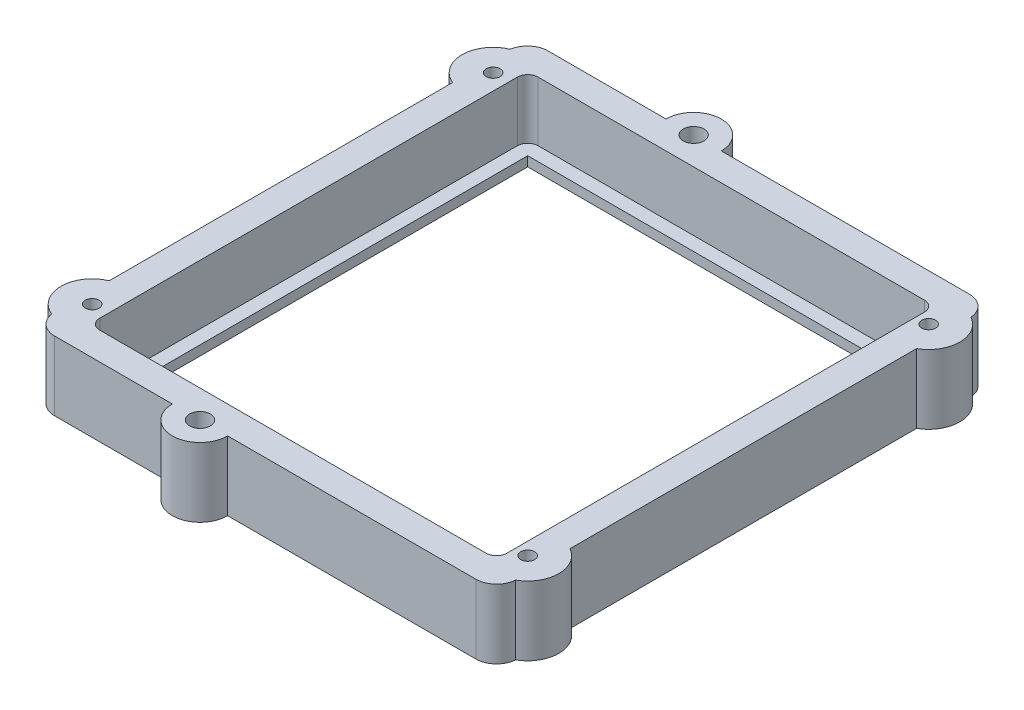
SolidWorks part; units mm, degrees
ref_plane "Спереди" through (0, 0, 0) normal (0, 0, 1) x (1, 0, 0)
ref_plane "Сверху" through (0, 0, 0) normal (0, 1, 0) x (1, 0, 0)
ref_plane "Справа" through (0, 0, 0) normal (1, 0, 0) x (0, 0, -1)
other "Configuration Table"
sketch "Эскиз1" plane through (0, 0, 0) normal (0, 1, 0) x (1, 0, 0)
  line L14 (-4, 4) -> (16, 4)
  line L21 (1.5, 0) -> (57.3857, 0)
  line L22 (0, -1.5) -> (0, -61.9)
  line L23 (1.5, -63.4) -> (57.3857, -63.4)
  line L24 (58.8857, -1.5) -> (58.8857, -61.9)
  line L25 (62.8857, 4) -> (62.8857, 1.2335)
  line L26 (-4, -67.4) -> (16, -67.4)
  line L27 (-4, 4) -> (-4, 1.4665)
  line L28 (-4, -6.8665) -> (-4, -56.5335)
  line L29 (-4, 4) -> (-4, -67.4) construction
  line L30 (62.8857, -6.6335) -> (62.8857, -56.7665)
  line L31 (62.8857, 4) -> (62.8857, -67.4) construction
  line L32 (62.8857, -64.6335) -> (62.8857, -67.4)
  line L33 (-4, -64.8665) -> (-4, -67.4)
  line L34 (0, 0) -> (0, -63.4) construction
  line L35 (0, -63.4) -> (58.8857, -63.4) construction
  line L36 (58.8857, 0) -> (58.8857, -63.4) construction
  line L37 (0, 0) -> (58.8857, 0) construction
  line L38 (20, 8.8001) -> (20, 2.5) construction
  line L39 (20, 0) -> (20, -67.4) construction
  line L40 (24, 4) -> (62.8857, 4)
  line L41 (-4, 4) -> (62.8857, 4) construction
  line L42 (24, -67.4) -> (62.8857, -67.4)
  line L43 (-4, -67.4) -> (62.8857, -67.4) construction
  line L44 (20, -68.9) -> (20, -77.3097) construction
  circle A8 centre (-2.3, -2.7) radius 1
  circle A9 centre (60.7, -2.7) radius 1
  circle A10 centre (60.7, -60.7) radius 1
  circle A11 centre (-2.3, -60.7) radius 1
  arc A12 (-4, 1.4665) -> (-4, -6.8665) centre (-2.3, -2.7) ccw
  arc A13 (62.8857, -6.6335) -> (62.8857, 1.2335) centre (60.7, -2.7) ccw
  arc A14 (62.8857, -64.6335) -> (62.8857, -56.7665) centre (60.7, -60.7) ccw
  arc A15 (-4, -56.5335) -> (-4, -64.8665) centre (-2.3, -60.7) ccw
  arc A16 (0, -61.9) -> (1.5, -63.4) centre (1.5, -61.9) ccw
  arc A17 (57.3857, -63.4) -> (58.8857, -61.9) centre (57.3857, -61.9) ccw
  arc A18 (57.3857, 0) -> (58.8857, -1.5) centre (57.3857, -1.5) cw
  arc A19 (1.5, 0) -> (0, -1.5) centre (1.5, -1.5) ccw
  arc A20 (24, 4) -> (16, 4) centre (20, 4) ccw
  arc A21 (16, -67.4) -> (24, -67.4) centre (20, -67.4) ccw
  circle A22 centre (20, -67.4) radius 1.5
  circle A23 centre (20, 4) radius 1.5
  dimension "D3" = 4
  dimension "D4" = 2
  dimension "D5" = 9
  dimension "D13" = 1.5
  dimension "D15" = 8
  dimension "D16" = 8
  dimension "D17" = 3
  dimension "D18" = 3
  dimension "D6" = 63
  dimension "D7" = 58
  dimension "D2" = 71.4
  dimension "D8" = 1.7
  dimension "D9" = 6.7
  dimension "D10" = 6.7
  dimension "D14" = 4
  dimension "D11" = 2
  dimension "D12" = 2
extrude "Бобышка-Вытянуть1" add sketch "Эскиз1" along normal blind 10
sketch "Эскиз2" [suppressed] plane through (0, 10, 0) normal (0, 1, 0) x (1, 0, 0)
  circle A0 centre (60.7, -60.7) radius 3.1
  circle A1 centre (60.7, -2.7) radius 3.1
  circle A2 centre (-2.3, -2.7) radius 3.1
  circle A3 centre (-2.3, -60.7) radius 3.1
  dimension "D1" = 6.2
sketch "Эскиз3" plane through (0, 0, 0) normal (0, -1, 0) x (1, 0, 0)
  line L0 (1.5, 63.4) -> (57.3857, 63.4) construction
  line L1 (0, 63.4) -> (58.8857, 63.4)
  line L2 (0, 63.4) -> (0, 0)
  line L3 (0, 0) -> (58.8857, 0)
  line L4 (58.8857, 63.4) -> (58.8857, 0)
  line L5 (58.8857, 61.9) -> (58.8857, 1.5) construction
  line L6 (57.3857, 0) -> (1.5, 0) construction
  line L7 (56.8857, 61.4) -> (56.8857, 2)
  line L8 (2, 2) -> (56.8857, 2)
  line L9 (2, 61.4) -> (2, 2)
  line L10 (2, 61.4) -> (56.8857, 61.4)
  dimension "D1" = 2
extrude "Бобышка-Вытянуть2" add sketch "Эскиз3" against normal blind 1.4
fillet "Скругление1" radius 3 4 edges at (62.8857, 5, 67.4) (-4, 5, 67.4) (62.8857, 5, -4) (-4, 5, -4)
